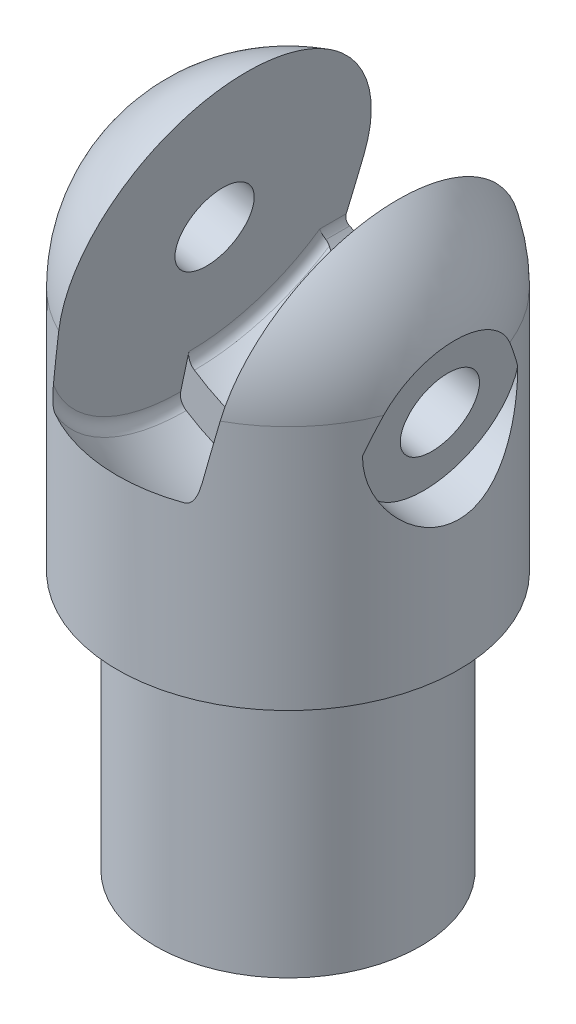
SolidWorks part; units mm, degrees
ref_plane "Front Plane" through (0, 0, 0) normal (0, 0, 1) x (1, 0, 0)
ref_plane "Top Plane" through (0, 0, 0) normal (0, 1, 0) x (1, 0, 0)
ref_plane "Right Plane" through (0, 0, 0) normal (1, 0, 0) x (0, 0, -1)
sketch "Sketch1" plane through (0, 0, 0) normal (0, 1, 0) x (1, 0, 0)
  circle A0 centre (0, 0) radius 12.9921
extrude "Boss-Extrude1" add sketch "Sketch1" along normal blind 25.4 contours A0
sketch "Sketch2" plane through (0, 0, 0) normal (1, 0, 0) x (0, 0, -1)
  line L0 (-16.764, 25.4) -> (-16.764, 49.53)
  line L1 (0, 25.4) -> (-16.764, 25.4)
  line L4 (12.9921, 25.4) -> (-12.9921, 25.4) construction
  line L5 (0, 14.2913) -> (0, -14.2913) construction
  line L6 (0, 25.4) -> (0, 66.294)
  arc A0 (0, 66.294) -> (-16.764, 49.53) centre (0, 49.53) ccw
  dimension "D1" = 33.528
  dimension "D2" = 24.13
revolve "Revolve1" add sketch "Sketch2" angle 360 about L6
ref_plane "Plane2" through (0, 49.53, 0) normal (0, -1, 0) x (-1, 0, 0)
ref_axis "Axis1" through (0, 49.53, 23.7) along (0, 0, -1)
ref_plane "Plane3" through (10.0728, 47.389, 0) normal (-0.2079, -0.9781, 0) x (0, 0, -1)
ref_plane "Plane4" through (-10.0728, 2.141, 0) normal (-0.9781, 0.2079, 0) x (0, 0, -1)
sketch "Sketch3" plane through (10.3665, 98.3003, 0) normal (-0.9781, 0.2079, 0) x (0, 0, -1)
  line L1 (-23.7, 49.8599) -> (13.1808, 49.8599) construction
  line L2 (0, 49.8599) -> (0, 73.4626) construction
  circle A2 centre (0, 49.8599) radius 3.81
  dimension "D1" = 7.62
extrude "Cut-Extrude1" cut sketch "Sketch3" against normal through all both and the other way through all
ref_axis "Axis2" through (14.5912, 46.4286, 0) along (-0.9781, 0.2079, 0)
sketch "Sketch10" plane through (0, 0, 0) normal (0, 0, 1) x (1, 0, 0)
  line L0 (14.5912, 46.4286) -> (-14.4718, 52.6061) construction
  line L1 (-7.205, 51.0615) -> (7.7019, 47.8929)
  point P5 (0.2484, 49.4772)
  dimension "D1" = 15.24
  dimension "D2" = 0.254
sketch "Sketch11" plane through (0, 0, 0) normal (0, 0, 1) x (1, 0, 0)
  line L2 (-7.205, 51.0615) -> (7.7019, 47.8929) construction
  line L3 (-7.205, 51.0615) -> (-3.696, 67.5703)
  line L4 (7.7019, 47.8929) -> (11.163, 64.1758)
  line L5 (-7.205, 51.0615) -> (7.7019, 47.8929)
  arc A0 (11.163, 64.1758) -> (-3.696, 67.5703) centre (0, 49.53) ccw
  arc A1 (16.7607, 49.8625) -> (-15.1764, 56.651) centre (0, 49.53) ccw construction
  dimension "D1" = 18.415
revolve "Cut-Revolve10" cut sketch "Sketch11" angle 90 about axis through (14.5912, 46.4286, 0) along (-0.9781, 0.2079, 0) other way angle 180
sketch "Sketch13" plane through (0, 0, 0) normal (0, 0, 1) x (1, 0, 0)
  line L0 (-6.4129, 54.7882) -> (8.4941, 51.6196)
  line L1 (-7.5306, 49.53) -> (-4.0741, 65.7914) construction
  line L2 (10.779, 62.3692) -> (8.0499, 49.53) construction
  line L3 (-7.205, 51.0615) -> (7.7019, 47.8929) construction
  line L4 (-6.4129, 54.7882) -> (-2.9274, 71.1864)
  line L5 (8.4941, 51.6196) -> (11.9796, 68.0178)
  arc A0 (11.9796, 68.0178) -> (-2.9274, 71.1864) centre (1.0406, 53.2039) ccw
  dimension "D1" = 3.81
  dimension "D2" = 36.83
revolve "Cut-Revolve11" cut sketch "Sketch13" angle 360 about L0
sketch "Sketch14" plane through (0, 0, 0) normal (0, 0, 1) x (1, 0, 0)
  line L0 (-7.205, 51.0615) -> (7.7019, 47.8929) construction
  line L1 (-7.205, 51.0615) -> (-8.7573, 43.7586)
  line L2 (7.7019, 47.8929) -> (6.1497, 40.59)
  line L3 (-7.205, 51.0615) -> (7.7019, 47.8929)
  arc A0 (-8.7573, 43.7586) -> (6.1497, 40.59) centre (0.2484, 49.4772) ccw
  dimension "D1" = 21.336
extrude "Cut-Extrude4" cut sketch "Sketch14" against normal blind 32.004
fillet "Fillet1" radius 1.27 6 edges at (-10.2986, 36.5075, 7.9665) (-9.6004, 39.7921, -6.7827) (-8.7573, 43.7586, -13.3502) (6.1497, 40.59, -14.0004) (5.3066, 36.6236, -6.7827) (4.84, 34.4287, 9.3615)
ref_plane "Plane5" through (-24.9798, 5.3096, 0) normal (-0.9781, 0.2079, 0) x (0, 0, -1)
sketch "Sketch15" plane through (-24.9798, 5.3096, 0) normal (-0.9781, 0.2079, 0) x (0, 0, -1)
  circle A0 centre (0, -48.4477) radius 7.62
  dimension "D1" = 15.24
extrude "Cut-Extrude5" cut sketch "Sketch15" along normal blind 10.16
mirror "Mirror1" about plane through (-10.0728, 2.141, 0) normal (-0.9781, 0.2079, 0) of "Cut-Extrude5"
